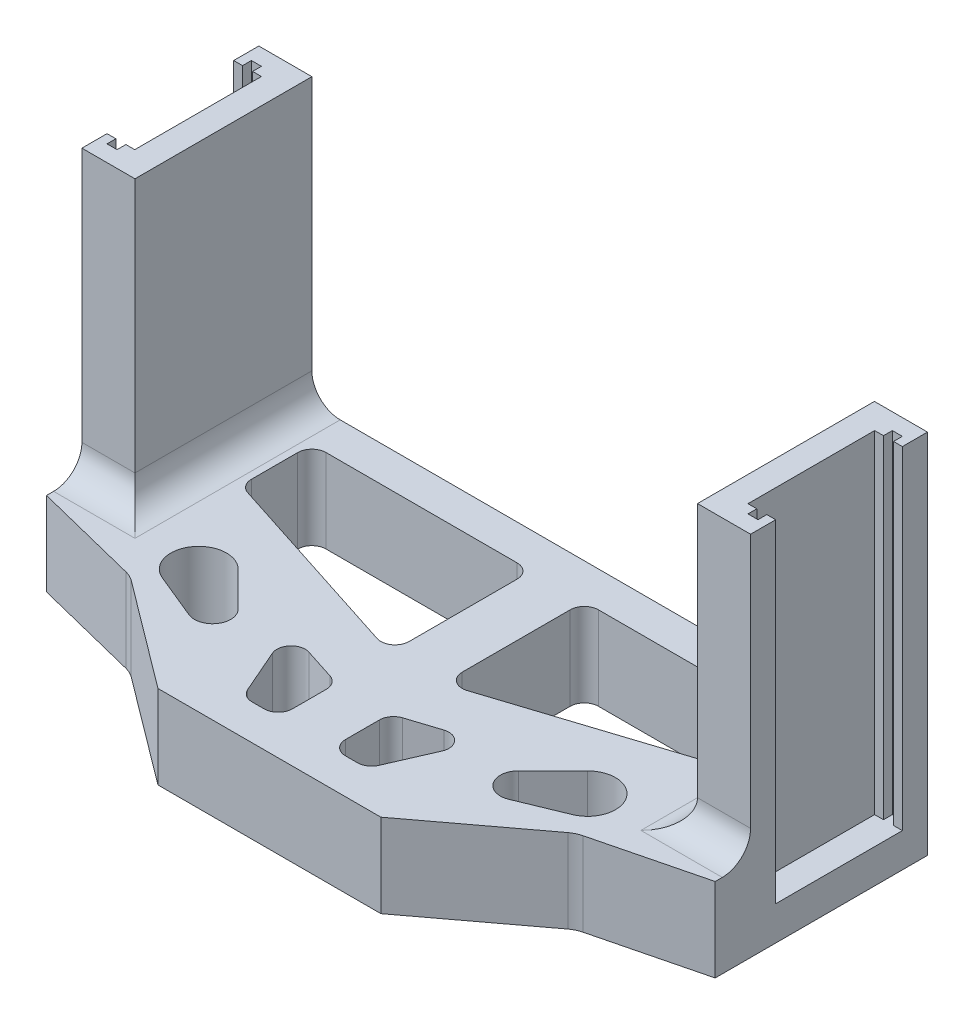
SolidWorks part; units mm, degrees
ref_plane "Front Plane" through (0, 0, 0) normal (0, 0, 1) x (1, 0, 0)
ref_plane "Top Plane" through (0, 0, 0) normal (0, 1, 0) x (1, 0, 0)
ref_plane "Right Plane" through (0, 0, 0) normal (1, 0, 0) x (0, 0, -1)
sketch "Sketch8" plane through (0, 0, 0) normal (0, 1, 0) x (1, 0, 0)
  line L0 (0, 55.3501) -> (0, -63.8655) construction
  line L1 (-20, -20) -> (20, -20)
  line L2 (60, 0) -> (-60, 0) construction
  line L3 (60, 0) -> (60, 38.1)
  line L4 (60, 38.1) -> (-60, 38.1)
  line L5 (-60, 0) -> (-60, 38.1)
  line L6 (20, -20) -> (40, -5)
  line L7 (40, -5) -> (60, 0)
  line L8 (-40, -5) -> (-60, 0)
  line L9 (-20, -20) -> (-40, -5)
  point P10 (0, -20)
  point P11 (0, 0)
  point P14 (0, 38.1)
  dimension "D1" = 20
  dimension "D2" = 40
  dimension "D3" = 20
  dimension "D4" = 38.1
  dimension "D5" = 15
  dimension "D6" = 25
extrude "Boss-Extrude4" add sketch "Sketch8" along normal blind 15 contours L4 L5 L8 L9 L1 L6 L7 L3
sketch "Sketch9" plane through (0, 15, 0) normal (0, 1, 0) x (1, 0, 0)
  line L0 (0, -24.776) -> (0, 46.0337) construction
  line L1 (-60, 0) -> (60, 0) construction
  line L2 (24.7447, -4.5511) -> (39.062, 4.9807) construction
  line L3 (-24.7447, -4.5511) -> (-39.062, 4.9807) construction
  line L4 (-30.7, -2.75) -> (30.7, -2.75) construction
  line L5 (39.9, 2.2098) -> (-39.9, 2.2098) construction
  line L6 (25.1547, -0.4491) -> (31.3688, 5.7497)
  line L7 (28.6873, -5.7553) -> (36.8036, -2.4136)
  line L8 (-28.6873, -5.7553) -> (-36.8036, -2.4136)
  line L9 (-25.1547, -0.4491) -> (-31.3688, 5.7497)
  line L10 (27.45, 0.5) -> (27.45, -6) construction
  line L11 (-20, -20) -> (20, -20) construction
  circle A0 centre (27.45, -2.75) radius 3.25 construction
  circle A1 centre (34.9, 2.2098) radius 5 construction
  circle A2 centre (-34.9, 2.2098) radius 5 construction
  circle A3 centre (-27.45, -2.75) radius 3.25 construction
  arc A4 (28.6873, -5.7553) -> (25.1547, -0.4491) centre (27.45, -2.75) cw
  arc A5 (31.3688, 5.7497) -> (36.8036, -2.4136) centre (34.9, 2.2098) cw
  arc A6 (-28.6873, -5.7553) -> (-25.1547, -0.4491) centre (-27.45, -2.75) ccw
  arc A7 (-31.3688, 5.7497) -> (-36.8036, -2.4136) centre (-34.9, 2.2098) ccw
  point P18 (24.2, -2.75)
  point P19 (-24.2, -2.75)
  dimension "D1" = 6.5
  dimension "D2" = 10
  dimension "D3" = 17.2
  dimension "D4" = 48.4
  dimension "D5" = 79.8
  dimension "D6" = 14
extrude "Cut-Extrude1" cut sketch "Sketch9" against normal through all
sketch "Sketch10" plane through (0, 15, 0) normal (0, 1, 0) x (1, 0, 0)
  line L1 (60, 38.1) -> (50.475, 38.1)
  line L2 (60, 38.1) -> (60, 6.35)
  line L3 (60, 6.35) -> (50.475, 6.35)
  line L4 (50.475, 38.1) -> (50.475, 6.35)
  dimension "D1" = 31.75
  dimension "D2" = 9.525
extrude "Boss-Extrude5" add sketch "Sketch10" along normal blind 50.8
sketch "Sketch11" plane through (0, 65.8, 0) normal (0, 1, 0) x (1, 0, 0)
  line L0 (60, 10.8585) -> (60, 33.5915)
  line L1 (60, 6.35) -> (60, 38.1) construction
  line L2 (60, 33.5915) -> (58.4125, 33.5915)
  line L3 (58.4125, 33.5915) -> (58.4125, 35.179)
  line L4 (58.4125, 35.179) -> (56.6125, 35.179)
  line L5 (56.6125, 35.179) -> (56.6125, 33.5915)
  line L6 (56.6125, 33.5915) -> (55.025, 33.5915)
  line L7 (55.025, 33.5915) -> (55.025, 10.8585)
  line L8 (50.475, 22.225) -> (60, 22.225) construction
  line L9 (50.475, 38.1) -> (50.475, 6.35) construction
  line L10 (56.6125, 10.8585) -> (55.025, 10.8585)
  line L11 (56.6125, 9.271) -> (56.6125, 10.8585)
  line L12 (58.4125, 9.271) -> (56.6125, 9.271)
  line L13 (58.4125, 10.8585) -> (58.4125, 9.271)
  line L14 (60, 10.8585) -> (58.4125, 10.8585)
  point P14 (55.025, 22.225)
  dimension "D1" = 25.908
  dimension "D2" = 1.5875
  dimension "D3" = 1.8
  dimension "D4" = 1.5875
  dimension "D5" = 1.5875
extrude "Cut-Extrude2" cut sketch "Sketch11" against normal blind 59.69
mirror "Mirror1" about plane through (0, 0, 0) normal (1, 0, 0) of "Boss-Extrude5", "Cut-Extrude2"
sketch "Sketch12" plane through (0, 15, 0) normal (0, 1, 0) x (1, 0, 0)
  line L0 (0, -20) -> (0, 38.1) construction
  line L1 (-20, -20) -> (20, -20) construction
  line L2 (50.475, 38.1) -> (-50.475, 38.1) construction
  line L3 (4.7625, 6.35) -> (44.125, 19.05)
  line L4 (44.125, 19.05) -> (44.125, 31.75)
  line L5 (44.125, 31.75) -> (4.7625, 31.75)
  line L6 (4.7625, 31.75) -> (4.7625, 6.35)
  line L7 (50.475, 38.1) -> (50.475, 6.35) construction
  line L8 (-4.7625, 31.75) -> (-4.7625, 6.35)
  line L9 (-44.125, 31.75) -> (-4.7625, 31.75)
  line L10 (-44.125, 19.05) -> (-44.125, 31.75)
  line L11 (-4.7625, 6.35) -> (-44.125, 19.05)
  line L12 (-4.7625, -3.175) -> (-17.4625, 0.9226)
  line L13 (-17.4625, 0.9226) -> (-11.1125, -13.65)
  line L14 (-11.1125, -13.65) -> (-4.7625, -13.65)
  line L15 (-4.7625, -13.65) -> (-4.7625, -3.175)
  line L16 (4.7625, -13.65) -> (4.7625, -3.175)
  line L17 (11.1125, -13.65) -> (4.7625, -13.65)
  line L18 (17.4625, 0.9226) -> (11.1125, -13.65)
  line L19 (4.7625, -3.175) -> (17.4625, 0.9226)
  dimension "D1" = 25.4
  dimension "D2" = 12.7
  dimension "D3" = 6.35
  dimension "D4" = 4.7625
  dimension "D5" = 6.35
  dimension "D6" = 9.525
  dimension "D7" = 6.35
  dimension "D8" = 12.7
  dimension "D9" = 6.35
extrude "Cut-Extrude3" cut sketch "Sketch12" against normal through all
fillet "Fillet2" radius 5.08 6 edges at (40, 7.5, 5) (-40, 7.5, 5) (-50.475, 15, -22.225) (-55.2375, 15, -6.35)
fillet "Fillet3" radius 2.54 16 edges at (-11.1125, 7.5, 13.65) (-4.7625, 7.5, 3.175) (-4.7625, 7.5, 13.65) (4.7625, 7.5, 13.65) (44.125, 7.5, -31.75) (44.125, 7.5, -19.05) (11.1125, 7.5, 13.65) (17.4625, 7.5, -0.9226) (4.7625, 7.5, 3.175) (4.7625, 7.5, -6.35) (-4.7625, 7.5, -6.35) (-17.4625, 7.5, -0.9226) (4.7625, 7.5, -31.75) (-4.7625, 7.5, -31.75) (-44.125, 7.5, -31.75) (-44.125, 7.5, -19.05)
